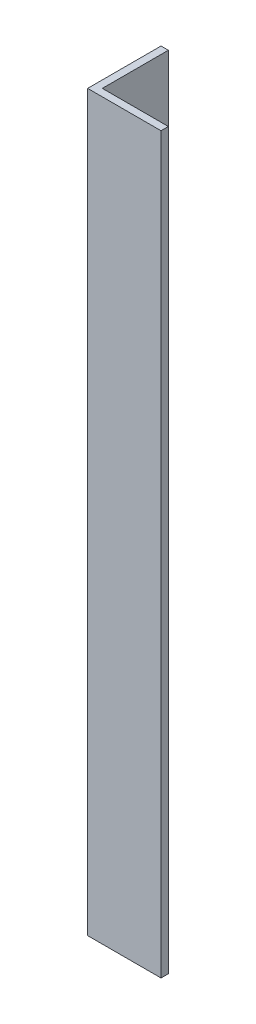
SolidWorks part; units mm, degrees
ref_plane "Спереди" through (0, 0, 0) normal (0, 0, 1) x (1, 0, 0)
ref_plane "Сверху" through (0, 0, 0) normal (0, 1, 0) x (1, 0, 0)
ref_plane "Справа" through (0, 0, 0) normal (1, 0, 0) x (0, 0, -1)
sketch "Эскиз1" plane through (0, 0, 0) normal (0, 1, 0) x (1, 0, 0)
  line L0 (0, 40) -> (0, 0)
  line L1 (0, 0) -> (40, 0)
extrude "Вытянуть-Тонкостенный1" add sketch "Эскиз1" along normal blind 400 thin thin type one direction reverse wall 4
